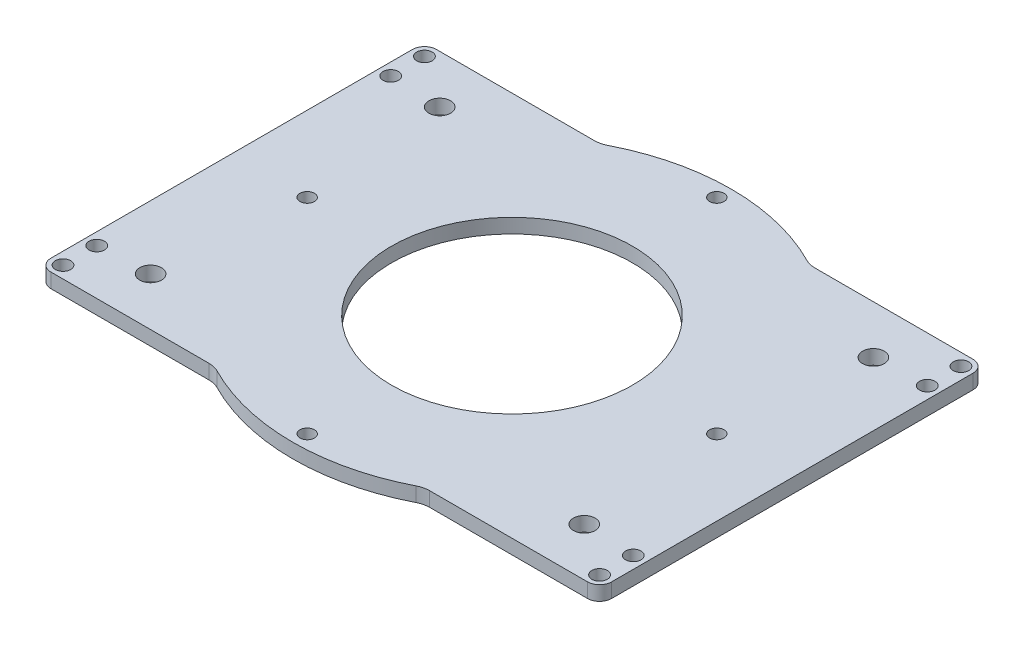
SolidWorks part; units mm, degrees
ref_plane "Front Plane" through (0, 0, 0) normal (0, 0, 1) x (1, 0, 0)
ref_plane "Top Plane" through (0, 0, 0) normal (0, 1, 0) x (1, 0, 0)
ref_plane "Right Plane" through (0, 0, 0) normal (1, 0, 0) x (0, 0, -1)
sketch "Sketch1" plane through (0, 0, 0) normal (0, 1, 0) x (1, 0, 0)
  line L0 (0, 0) -> (0, 42.5) construction
  line L1 (45, -30) -> (-45, -30) construction
  line L2 (45, -30) -> (45, 30) construction
  line L3 (45, 30) -> (-45, 30) construction
  line L4 (-45, -30) -> (-45, 30) construction
  line L5 (45, -30) -> (-45, 30) construction
  line L6 (45, 30) -> (-45, -30) construction
  line L7 (55.675, -40) -> (-55.675, -40) construction
  line L8 (58.175, -37.5) -> (58.175, 37.5)
  line L9 (55.675, 40) -> (-55.675, 40) construction
  line L10 (-58.175, -37.5) -> (-58.175, 37.5)
  line L11 (58.175, -40) -> (-58.175, 40) construction
  line L12 (58.175, 40) -> (-58.175, -40) construction
  line L13 (0, 0) -> (42.5, 0) construction
  line L14 (-55.675, 40) -> (-22.9183, 40)
  line L15 (22.9183, 40) -> (55.675, 40)
  line L16 (22.9183, -40) -> (55.675, -40)
  line L17 (-55.675, -40) -> (-22.9183, -40)
  line L18 (55.675, 37.5) -> (55.675, 30.5) construction
  line L20 (55.675, 37.5) -> (55.675, 40) construction
  circle A0 centre (-45, 30) radius 2.25
  circle A1 centre (-45, -30) radius 2.25
  circle A2 centre (45, -30) radius 2.25
  circle A3 centre (45, 30) radius 2.25
  circle A4 centre (0, 0) radius 25
  arc A5 (-58.175, -37.5) -> (-55.675, -40) centre (-55.675, -37.5) ccw
  arc A6 (55.675, -40) -> (58.175, -37.5) centre (55.675, -37.5) ccw
  arc A7 (58.175, 37.5) -> (55.675, 40) centre (55.675, 37.5) ccw
  arc A8 (-55.675, 40) -> (-58.175, 37.5) centre (-55.675, 37.5) ccw
  circle A9 centre (0, 0) radius 42.5 construction
  circle A10 centre (0, 42.5) radius 1.5
  circle A11 centre (42.5, 0) radius 1.5
  circle A12 centre (0, -42.5) radius 1.5
  circle A13 centre (-42.5, 0) radius 1.5
  arc A14 (20.6492, 40.5446) -> (-20.6492, 40.5446) centre (0, 0) ccw
  arc A15 (22.9183, 40) -> (20.6492, 40.5446) centre (22.9183, 45) cw
  arc A16 (-20.6492, 40.5446) -> (-22.9183, 40) centre (-22.9183, 45) cw
  arc A17 (22.9183, -40) -> (20.6492, -40.5446) centre (22.9183, -45) ccw
  arc A18 (20.6492, -40.5446) -> (-20.6492, -40.5446) centre (0, 0) cw
  arc A19 (-20.6492, -40.5446) -> (-22.9183, -40) centre (-22.9183, -45) ccw
  circle A20 centre (55.675, 37.5) radius 1.6
  circle A21 centre (55.675, 30.5) radius 1.6
  circle A22 centre (-55.675, 30.5) radius 1.6
  circle A23 centre (-55.675, 37.5) radius 1.6
  circle A24 centre (-55.675, -37.5) radius 1.6
  circle A25 centre (-55.675, -30.5) radius 1.6
  circle A26 centre (55.675, -37.5) radius 1.6
  circle A27 centre (55.675, -30.5) radius 1.6
  point P0 (0, 0)
  point P18 (-55.675, -37.5)
  point P41 (21.6852, 40)
  point P44 (-21.6852, 40)
  point P53 (53.9389, -30.5)
  point P57 (0, 0)
  point P58 (0, 0)
  dimension "D1" = 4.5
  dimension "D4" = 50
  dimension "D7" = 2
  dimension "D8" = 85
  dimension "D9" = 3
  dimension "D10" = 3
  dimension "D11" = 5
  dimension "D5" = 40
  dimension "D12" = 3.2
  dimension "D2" = 90
  dimension "D3" = 60
  dimension "D6" = 116.35
  dimension "D13" = 7
  dimension "D14" = 2.5
  dimension "D15" = 2.5
  dimension "D16" = 2
extrude "Boss-Extrude1" add sketch "Sketch1" along normal blind 3
